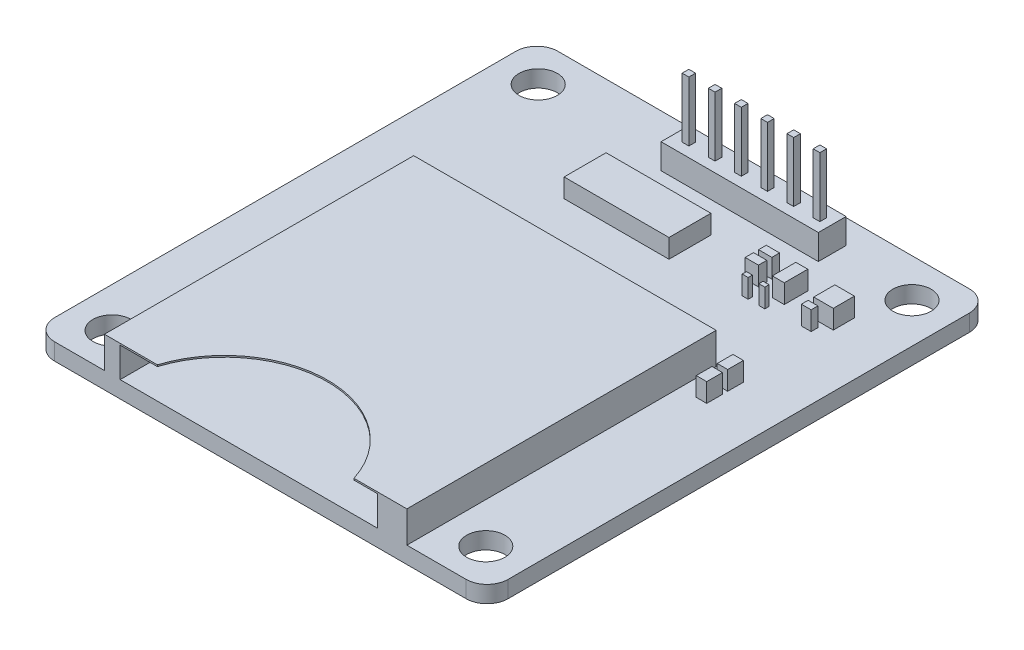
SolidWorks part; units mm, degrees
material "policarbonato"
ref_plane "Alzado" through (0, 0, 0) normal (0, 0, 1) x (1, 0, 0)
ref_plane "Planta" through (0, 0, 0) normal (0, 1, 0) x (1, 0, 0)
ref_plane "Vista lateral" through (0, 0, 0) normal (1, 0, 0) x (0, 0, -1)
sketch "Sketch1" plane through (0, 0, 0) normal (0, 1, 0) x (1, 0, 0)
  line L0 (3.8, 44.325) -> (39.45, 44.325) construction
  line L1 (0, 0) -> (43.25, 0)
  line L2 (0, 0) -> (0, 48)
  line L3 (0, 48) -> (43.25, 48)
  line L4 (43.25, 0) -> (43.25, 48)
  line L5 (39.45, 44.325) -> (39.45, 3.675) construction
  line L6 (39.45, 3.675) -> (3.8, 3.675) construction
  line L7 (3.8, 3.675) -> (3.8, 44.325) construction
  line L8 (21.625, 44.325) -> (21.625, 48) construction
  line L9 (39.45, 24) -> (43.25, 24) construction
  circle A0 centre (3.8, 44.325) radius 1.825
  circle A1 centre (3.8, 3.675) radius 1.825
  circle A2 centre (39.45, 44.325) radius 1.825
  circle A3 centre (39.45, 3.675) radius 1.825
  dimension "D3" = 3.65
  dimension "D4" = 32
  dimension "D5" = 37
  dimension "D6" = 40.65
  dimension "D7" = 35.65
  dimension "D1" = 43.25
  dimension "D2" = 48
extrude "Boss-Extrude1" add sketch "Sketch1" along normal blind 1.6
sketch "Sketch2" plane through (0, 1.6, 0) normal (0, 1, 0) x (1, 0, 0)
  line L0 (0, 0) -> (43.25, 0) construction
  line L1 (6.75, 0) -> (11.8, 0)
  line L2 (6.75, 0) -> (6.75, 29.5)
  line L3 (6.75, 29.5) -> (35.6, 29.5)
  line L4 (35.6, 0) -> (35.6, 29.5)
  line L6 (21.175, 29.5) -> (21.175, 0) construction
  line L7 (30.55, 0) -> (35.6, 0)
  line L9 (0, 48) -> (0, 0) construction
  arc A0 (11.8, 0) -> (30.55, 0) centre (21.175, -2.976) cw
  point P9 (21.175, 6.86)
  dimension "D1" = 6.75
  dimension "D2" = 29.5
  dimension "D3" = 6.86
  dimension "D4" = 18.75
  dimension "D5" = 28.85
extrude "Boss-Extrude2" add sketch "Sketch2" along normal offset from surface (3 mm away) 4.6 up to face at (39.45, 0, -42.5)
sketch "Sketch3" plane through (0, 0, 0) normal (0, 0, 1) x (1, 0, 0)
  line L0 (30.55, 1.6) -> (11.8, 1.6) construction
  line L1 (8.25, 1.6) -> (32.8, 1.6)
  line L2 (8.25, 1.6) -> (8.25, 4.45)
  line L3 (8.25, 4.45) -> (32.8, 4.45)
  line L4 (32.8, 1.6) -> (32.8, 4.45)
  line L5 (6.75, 4.6) -> (11.8, 4.6) construction
  line L6 (35.6, 4.6) -> (35.6, 1.6) construction
  line L7 (6.75, 4.6) -> (6.75, 1.6) construction
  point P8 (35.6, 3.1)
  dimension "D1" = 0.15
  dimension "D2" = 2.8
  dimension "D3" = 1.5
extrude "Cut-Extrude1" cut sketch "Sketch3" against normal blind 21.6
sketch "Sketch5" plane through (0, 1.6, 0) normal (0, 1, 0) x (1, 0, 0)
  line L1 (16.794, 45.7) -> (31.794, 45.7)
  line L2 (16.794, 45.7) -> (16.794, 43.05)
  line L3 (16.794, 43.05) -> (31.794, 43.05)
  line L4 (31.794, 45.7) -> (31.794, 43.05)
  line L9 (43.25, 48) -> (0, 48) construction
  point P4 (16.794, 43.05)
  dimension "D1" = 15
  dimension "D2" = 2.65
  dimension "D6" = 2.3
extrude "Boss-Extrude4" add sketch "Sketch5" along normal blind 2.4
sketch "Sketch6" plane through (0, 4, 0) normal (0, 1, 0) x (1, 0, 0)
  line L0 (16.794, 45.7) -> (16.794, 43.05) construction
  line L1 (17.834, 44.66) -> (18.474, 44.66)
  line L2 (17.834, 44.66) -> (17.834, 44.02)
  line L3 (17.834, 44.02) -> (18.474, 44.02)
  line L4 (18.474, 44.66) -> (18.474, 44.02)
  line L5 (31.794, 45.7) -> (16.794, 45.7) construction
  line L6 (20.334, 44.02) -> (20.974, 44.02)
  line L7 (20.334, 44.66) -> (20.334, 44.02)
  line L8 (20.334, 44.66) -> (20.974, 44.66)
  line L9 (20.974, 44.66) -> (20.974, 44.02)
  line L10 (22.834, 44.02) -> (23.474, 44.02)
  line L11 (22.834, 44.66) -> (22.834, 44.02)
  line L12 (22.834, 44.66) -> (23.474, 44.66)
  line L13 (23.474, 44.66) -> (23.474, 44.02)
  line L14 (25.334, 44.02) -> (25.974, 44.02)
  line L15 (25.334, 44.66) -> (25.334, 44.02)
  line L16 (25.334, 44.66) -> (25.974, 44.66)
  line L17 (25.974, 44.66) -> (25.974, 44.02)
  line L18 (27.834, 44.02) -> (28.474, 44.02)
  line L19 (27.834, 44.66) -> (27.834, 44.02)
  line L20 (27.834, 44.66) -> (28.474, 44.66)
  line L21 (28.474, 44.66) -> (28.474, 44.02)
  line L22 (30.334, 44.02) -> (30.974, 44.02)
  line L23 (30.334, 44.66) -> (30.334, 44.02)
  line L24 (30.334, 44.66) -> (30.974, 44.66)
  line L25 (30.974, 44.66) -> (30.974, 44.02)
  dimension "D1" = 0.64
  dimension "D2" = 0.64
  dimension "D3" = 1.04
  dimension "D4" = 1.04
  dimension "D5" = 6
extrude "Boss-Extrude5" add sketch "Sketch6" along normal blind 5.7
fillet "Fillet1" radius 2 4 edges at (0, 0.8, 0) (43.25, 0.8, 0) (43.25, 0.8, -48) (0, 0.8, -48)
sketch "Sketch8" plane through (0, 0, 0) normal (0, 0, 1) x (1, 0, 0)
  line L0 (20.525, 1.95) -> (20.525, 1.6) construction
  line L1 (8.525, 1.95) -> (32.525, 1.95)
  line L2 (8.525, 1.95) -> (8.525, 3.95)
  line L3 (8.525, 3.95) -> (32.525, 3.95)
  line L4 (32.525, 1.95) -> (32.525, 3.95)
  line L5 (8.25, 1.6) -> (32.8, 1.6) construction
  line L6 (2, 0) -> (41.25, 0) construction
  dimension "D1" = 24
  dimension "D2" = 2
  dimension "D3" = 1.95
extrude "Boss-Extrude7" [suppressed] add sketch "Sketch8" along normal blind 5.6 and the other way blind 26.3
sketch "Croquis1" plane through (0, 1.6, 0) normal (0, 1, 0) x (1, 0, 0)
  line L0 (37.1885, 27.5099) -> (38.1885, 27.5099)
  line L1 (14.4802, 36.1166) -> (24.4802, 36.1166)
  line L2 (14.4802, 36.1166) -> (14.4802, 40.1166)
  line L3 (14.4802, 40.1166) -> (24.4802, 40.1166)
  line L4 (24.4802, 36.1166) -> (24.4802, 40.1166)
  line L5 (29.7626, 39.3825) -> (31.0306, 39.3825)
  line L6 (29.7626, 39.3825) -> (29.7626, 40.1166)
  line L7 (29.7626, 40.1166) -> (31.0306, 40.1166)
  line L8 (31.0306, 39.3825) -> (31.0306, 40.1166)
  line L9 (29.7626, 38.0995) -> (31.0306, 38.0995)
  line L10 (29.7626, 38.0995) -> (29.7626, 38.8977)
  line L11 (29.7626, 38.8977) -> (31.0306, 38.8977)
  line L12 (31.0306, 38.0995) -> (31.0306, 38.8977)
  line L13 (32.5818, 40.1166) -> (33.7219, 40.1166)
  line L14 (32.5818, 40.1166) -> (32.5818, 37.8715)
  line L15 (32.5818, 37.8715) -> (33.7219, 37.8715)
  line L16 (33.7219, 40.1166) -> (33.7219, 37.8715)
  line L17 (36.3063, 40.1166) -> (38.1686, 40.1166)
  line L18 (36.3063, 40.1166) -> (36.3063, 38.0995)
  line L19 (36.3063, 38.0995) -> (38.1686, 38.0995)
  line L20 (38.1686, 40.1166) -> (38.1686, 38.0995)
  line L21 (36.3063, 37.5675) -> (37.2375, 37.5675)
  line L22 (36.3063, 37.5675) -> (36.3063, 36.9214)
  line L23 (36.3063, 36.9214) -> (37.2375, 36.9214)
  line L24 (37.2375, 37.5675) -> (37.2375, 36.9214)
  line L25 (32.5818, 36.9895) -> (33.1523, 36.9895)
  line L26 (32.5818, 36.9895) -> (32.5818, 36.5862)
  line L27 (32.5818, 36.5862) -> (33.1523, 36.5862)
  line L28 (33.1523, 36.9895) -> (33.1523, 36.5862)
  line L29 (37.1885, 29.5099) -> (38.1885, 29.5099)
  line L30 (37.1885, 29.5099) -> (37.1885, 28.0099)
  line L31 (37.1885, 28.0099) -> (38.1885, 28.0099)
  line L32 (38.1885, 29.5099) -> (38.1885, 28.0099)
  line L33 (37.1885, 27.5099) -> (37.1885, 26.0099)
  line L34 (37.1885, 26.0099) -> (38.1885, 26.0099)
  line L35 (38.1885, 27.5099) -> (38.1885, 26.0099)
  line L37 (30.9918, 36.5862) -> (31.5623, 36.5862)
  line L38 (30.9918, 36.5862) -> (30.9918, 36.9895)
  line L39 (30.9918, 36.9895) -> (31.5623, 36.9895)
  line L40 (31.5623, 36.5862) -> (31.5623, 36.9895)
  dimension "D1" = 10
  dimension "D2" = 4
  dimension "D3" = 1.5
  dimension "D4" = 1
  dimension "D5" = 1.5
  dimension "D6" = 1
extrude "Saliente-Extruir1" add sketch "Croquis1" along normal blind 1.8
